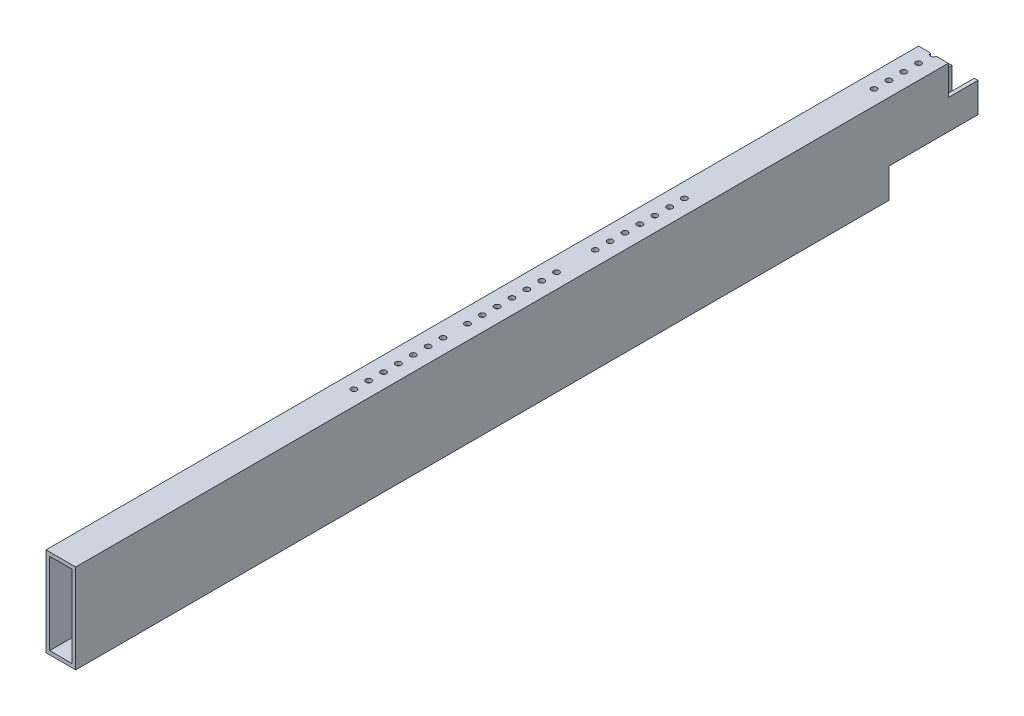
SolidWorks part; units mm, degrees
ref_plane "Front Plane" through (0, 0, 0) normal (0, 0, 1) x (1, 0, 0)
ref_plane "Top Plane" through (0, 0, 0) normal (0, 1, 0) x (1, 0, 0)
ref_plane "Right Plane" through (0, 0, 0) normal (1, 0, 0) x (0, 0, -1)
sketch "Sketch1" plane through (0, 0, 0) normal (0, 0, 1) x (1, 0, 0)
  line L1 (-12.7, -38.1) -> (12.7, -38.1)
  line L2 (-12.7, -38.1) -> (-12.7, 38.1)
  line L3 (-12.7, 38.1) -> (12.7, 38.1)
  line L4 (12.7, -38.1) -> (12.7, 38.1)
  line L5 (-12.7, -38.1) -> (12.7, 38.1) construction
  line L6 (-12.7, 38.1) -> (12.7, -38.1) construction
  point P0 (0, 0)
  dimension "D1" = 25.4
  dimension "D2" = 76.2
extrude "Boss-Extrude1" add sketch "Sketch1" along normal mid plane 771.398
shell "Shell1" thickness 3.175 removed face at (0, 0, -385.699) removed face at (0, 0, 385.699)
sketch "Sketch2" plane through (12.7, 0, 0) normal (1, 0, 0) x (0, 0, -1)
  line L1 (385.699, -38.1) -> (309.499, -38.1)
  line L2 (385.699, -38.1) -> (385.699, -12.7)
  line L3 (385.699, -12.7) -> (309.499, -12.7)
  line L4 (309.499, -38.1) -> (309.499, -12.7)
  dimension "D1" = 25.4
  dimension "D2" = 76.2
extrude "Cut-Extrude1" cut sketch "Sketch2" against normal through all
sketch "Sketch3" plane through (12.7, 0, 0) normal (1, 0, 0) x (0, 0, -1)
  line L1 (385.699, 38.1) -> (360.299, 38.1)
  line L2 (385.699, 38.1) -> (385.699, 12.7)
  line L3 (385.699, 12.7) -> (360.299, 12.7)
  line L4 (360.299, 38.1) -> (360.299, 12.7)
  dimension "D1" = 25.4
extrude "Cut-Extrude2" cut sketch "Sketch3" against normal through all
sketch "Sketch4" plane through (0, 38.1, 0) normal (0, 1, 0) x (1, 0, 0)
  line L0 (-12.7, 360.299) -> (12.7, 360.299) construction
  circle A0 centre (0, 147.3945) radius 2.3812
  circle A1 centre (0, 134.6945) radius 2.3812
  circle A2 centre (0, 121.9945) radius 2.3812
  circle A3 centre (0, 109.2945) radius 2.3812
  circle A4 centre (0, 96.5945) radius 2.3812
  circle A5 centre (0, 83.8945) radius 2.3812
  circle A6 centre (0, 71.1945) radius 2.3812
  circle A7 centre (0, 38.0987) radius 2.3812
  circle A8 centre (0, 25.3987) radius 2.3813
  circle A9 centre (0, 12.6987) radius 2.3813
  circle A10 centre (0, -0.0013) radius 2.3813
  circle A11 centre (0, -12.7013) radius 2.3812
  circle A12 centre (0, -25.4013) radius 2.3812
  circle A13 centre (0, -38.1013) radius 2.3812
  circle A15 centre (0, -58.9932) radius 2.3812
  circle A16 centre (0, -71.6932) radius 2.3812
  circle A17 centre (0, -84.3932) radius 2.3812
  circle A18 centre (0, -97.0932) radius 2.3812
  circle A19 centre (0, -109.7932) radius 2.3812
  circle A20 centre (0, -122.4932) radius 2.3812
  circle A21 centre (0, -135.1932) radius 2.3813
  point P33 (0, 360.299)
  dimension "D1" = 4.7625
  dimension "D3" = 12.7
  dimension "D4" = 12.7
  dimension "D5" = 12.7
  dimension "D6" = 12.7
  dimension "D7" = 12.7
  dimension "D8" = 12.7
  dimension "D9" = 322.2003
  dimension "D10" = 12.7
  dimension "D11" = 12.7
  dimension "D12" = 12.7
  dimension "D13" = 12.7
  dimension "D14" = 12.7
  dimension "D15" = 12.7
  dimension "D16" = 12.7
  dimension "D17" = 419.2922
  dimension "D18" = 12.7
  dimension "D19" = 12.7
  dimension "D20" = 12.7
  dimension "D21" = 12.7
  dimension "D22" = 12.7
  dimension "D2" = 212.9045
extrude "Cut-Extrude3" cut sketch "Sketch4" against normal up to next
sketch "Sketch5" plane through (0, 38.1, 0) normal (0, 1, 0) x (1, 0, 0)
  line L0 (-12.7, 360.299) -> (12.7, 360.299) construction
  circle A0 centre (0, 360.299) radius 2.3813
  circle A1 centre (0, 347.599) radius 2.3813
  circle A2 centre (0, 334.899) radius 2.3813
  circle A3 centre (0, 322.199) radius 2.3813
  circle A4 centre (0, 309.499) radius 2.3813
  dimension "D1" = 4.7625
  dimension "D3" = 12.7
  dimension "D4" = 12.7
  dimension "D5" = 12.7
  dimension "D8" = 0
  dimension "D2" = 12.7
extrude "Cut-Extrude4" cut sketch "Sketch5" against normal up to next
sketch "Sketch6" plane through (0, -38.1, 0) normal (0, -1, 0) x (1, 0, 0)
  line L0 (-12.7, -309.499) -> (12.7, -309.499) construction
  circle A0 centre (0, -309.499) radius 2.3813
  circle A1 centre (0, -296.799) radius 2.3813
  circle A2 centre (0, -284.099) radius 2.3813
  circle A3 centre (0, -258.699) radius 2.3813
  circle A6 centre (0, -271.399) radius 2.3813
  dimension "D1" = 4.7625
  dimension "D2" = 12.7
  dimension "D3" = 12.7
  dimension "D4" = 12.7
  dimension "D5" = 12.7
  dimension "D6" = 0
extrude "Cut-Extrude5" cut sketch "Sketch6" against normal up to next
sketch3d "3DSketch1" [suppressed]
  line L0 (0, 34.925, -109.2945) -> (0, 38.1, -109.2945) construction
  line L1 (0, 34.925, 97.0932) -> (0, 38.1, 97.0932) construction
  point P0 (0, 38.1, -109.2945)
  point P1 (0, 0, 0)
  point P4 (0, 38.1, 97.0932)
